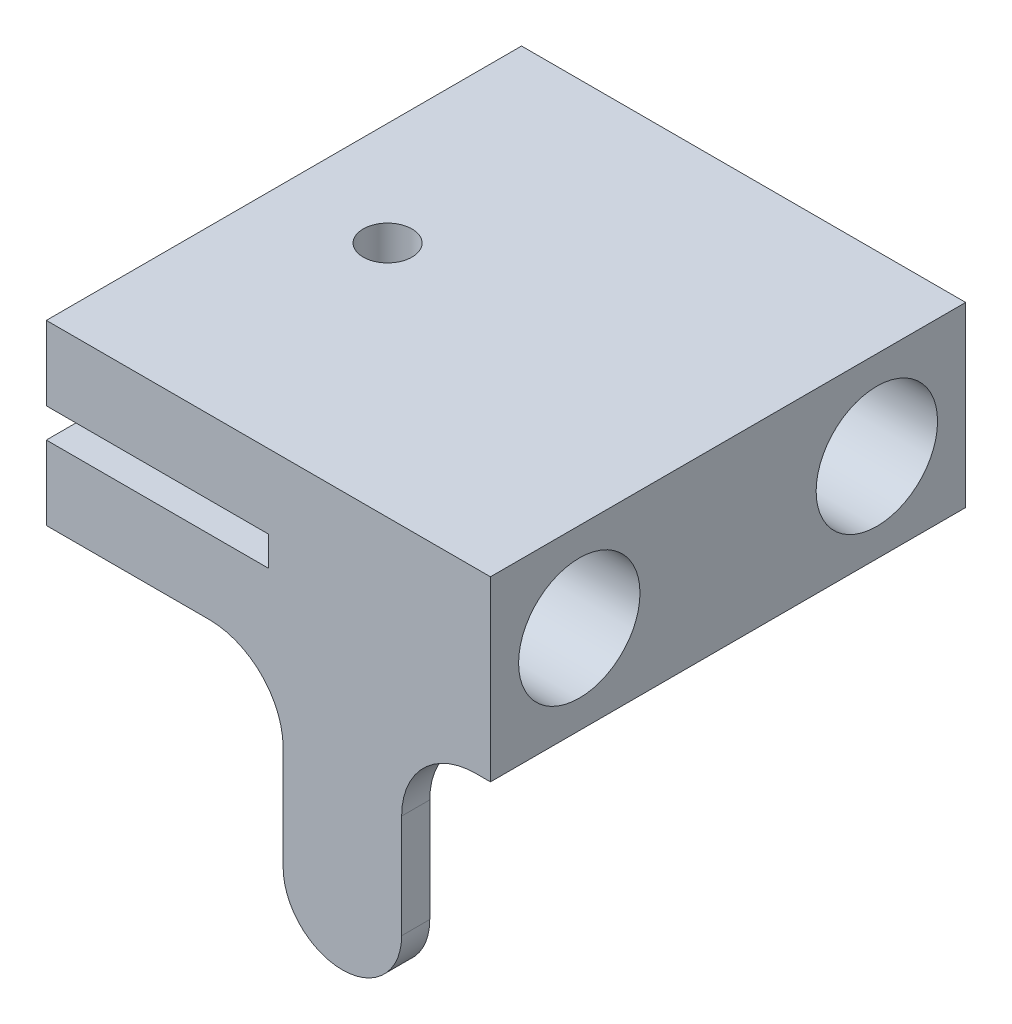
SolidWorks part; units mm, degrees
ref_plane "Alzado" through (0, 0, 0) normal (0, 0, 1) x (1, 0, 0)
ref_plane "Planta" through (0, 0, 0) normal (0, 1, 0) x (1, 0, 0)
ref_plane "Vista lateral" through (0, 0, 0) normal (1, 0, 0) x (0, 0, -1)
sketch "Croquis1" plane through (0, 0, 0) normal (1, 0, 0) x (0, 0, -1)
  line L0 (-10.05, 0) -> (10.05, 0)
  line L2 (-16.05, -6) -> (16.05, -6)
  line L3 (-16.05, -6) -> (-16.05, 6)
  line L4 (-16.05, 6) -> (16.05, 6)
  line L5 (16.05, -6) -> (16.05, 6)
  line L6 (-16.05, -6) -> (16.05, 6) construction
  line L7 (-16.05, 6) -> (16.05, -6) construction
  circle A0 centre (-10.05, 0) radius 4.1
  circle A1 centre (10.05, 0) radius 4.1
  point P4 (0, 0)
  point P7 (0, 0)
extrude "Saliente-Extruir1" add sketch "Croquis1" along normal blind 30 contours L2 L5 L4 L3 A1 A0 region at (0, 0, 15.7073)
sketch "Croquis2" plane through (0, 0, 16.05) normal (0, 0, 1) x (1, 0, 0)
  line L0 (0, 0) -> (15, 0) construction
  line L1 (0, -6) -> (0, 6) construction
  line L2 (15, 1) -> (15, -1)
  line L4 (15, 1) -> (0, 1)
  line L5 (15, 1) -> (15, -1)
  line L6 (15, -1) -> (0, -1)
  line L7 (0, 1) -> (0, -1)
  point P7 (15, 0)
extrude "Cortar-Extruir2" cut sketch "Croquis2" against normal blind 33 contours L0 L7 L6 L5 | L2 L0 L4 region at (7.5, 0.5, 16.05) region at (7.5, -0.5, 16.05)
sketch "Croquis4" plane through (0, 6, 0) normal (0, 1, 0) x (1, 0, 0)
  line L0 (0, 0) -> (7, 0) construction
  line L1 (0, -16.05) -> (0, 16.05) construction
  circle A0 centre (7, 0) radius 1.65
extrude "Cortar-Extruir3" cut sketch "Croquis4" against normal blind 12
sketch "Croquis5" plane through (0, -6, 0) normal (0, -1, 0) x (1, 0, 0)
  circle A0 centre (7, 0) radius 3.1
extrude "Cortar-Extruir4" cut sketch "Croquis5" against normal blind 2
sketch "Croquis7" plane through (0, -6, 0) normal (0, -1, 0) x (1, 0, 0)
  line L0 (0, 16.05) -> (20, 16.05) construction
  line L1 (30, 16.05) -> (0, 16.05) construction
  line L2 (20, 16.05) -> (20, 14.15) construction
  line L3 (20, 14.15) -> (24, 14.15)
  line L4 (24, 14.15) -> (24, 16.05)
  line L5 (24, 16.05) -> (15.9955, 16.05)
  line L6 (15.9955, 16.05) -> (15.9955, 14.15)
  line L7 (15.9955, 14.15) -> (20, 14.15)
extrude "Saliente-Extruir2" add sketch "Croquis7" along normal blind 16
fillet "Redondeo1" radius 5 1 edges at (15.9955, -6, 15.1) type face fillet first side face at (15.9955, -14, 15.1) second side face at (7, -6, -3.1)
fillet "Redondeo2" radius 5 1 edges at (24, -6, 15.1) type face fillet first side face at (7, -6, -3.1) second side face at (24, -14, 15.1)
fillet "Redondeo3" 2 edges at (15.9955, -22, 15.1) (24, -22, 15.1) type full round first side face at (15.9955, -16.5, 15.1) second side face at (24, -16.5, 15.1) middle face at (19.9977, -22, 15.1)
